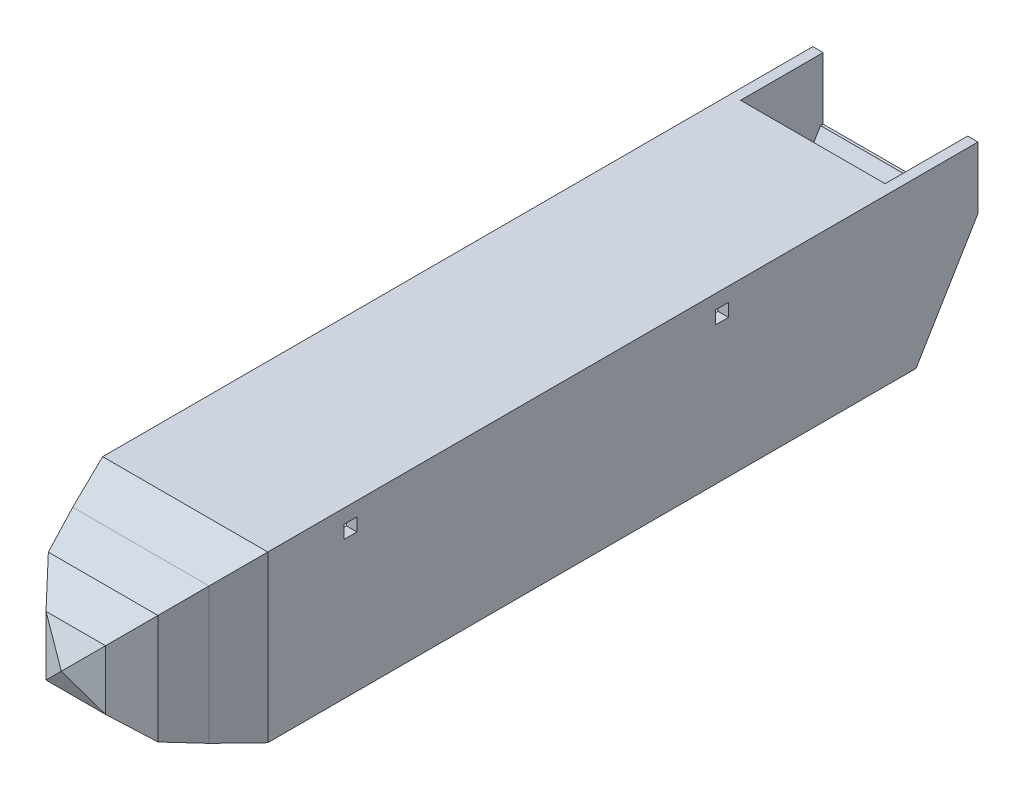
SolidWorks part; units mm, degrees
material "Balsa"
ref_plane "Front Plane" through (0, 0, 0) normal (0, 0, 1) x (1, 0, 0)
ref_plane "Top Plane" through (0, 0, 0) normal (0, 1, 0) x (1, 0, 0)
ref_plane "Right Plane" through (0, 0, 0) normal (1, 0, 0) x (0, 0, -1)
sketch "Sketch1" plane through (0, 0, 0) normal (0, 0, 1) x (1, 0, 0)
  line L1 (-50.8, -50.8) -> (50.8, -50.8)
  line L2 (-50.8, -50.8) -> (-50.8, 50.8)
  line L3 (-50.8, 50.8) -> (50.8, 50.8)
  line L4 (50.8, -50.8) -> (50.8, 50.8)
  line L5 (-50.8, -50.8) -> (50.8, 50.8) construction
  line L6 (-50.8, 50.8) -> (50.8, -50.8) construction
  point P0 (0, 0)
  dimension "D1" = 101.6
extrude "Boss-Extrude1" add sketch "Sketch1" along normal blind 436.88 contours L2 L1 L4 L3
ref_plane "Plane1" through (0, 0, 464.1566) normal (0, 0, 1) x (1, 0, 0)
sketch "Sketch3" plane through (0, 0, 464.1566) normal (0, 0, 1) x (1, 0, 0)
  line L1 (-41.9373, -41.9373) -> (41.9373, -41.9373)
  line L2 (-41.9373, -41.9373) -> (-41.9373, 41.9373)
  line L3 (-41.9373, 41.9373) -> (41.9373, 41.9373)
  line L4 (41.9373, -41.9373) -> (41.9373, 41.9373)
  line L5 (-41.9373, -41.9373) -> (41.9373, 41.9373) construction
  line L6 (-41.9373, 41.9373) -> (41.9373, -41.9373) construction
  point P0 (0, 0)
  dimension "D1" = 83.8746
  dimension "D2" = 83.8746
sketch "Sketch5" plane through (0, 0, 436.88) normal (0, 0, 1) x (1, 0, 0)
  line L0 (50.8, -50.8) -> (50.8, 50.8) construction
  line L1 (-50.8, 50.8) -> (50.8, 50.8) construction
  line L2 (-50.8, -50.8) -> (-50.8, 50.8) construction
  line L3 (-50.8, -50.8) -> (50.8, -50.8) construction
  line L4 (50.8, -50.8) -> (50.8, 50.8)
  line L5 (-50.8, 50.8) -> (50.8, 50.8)
  line L6 (-50.8, -50.8) -> (-50.8, 50.8)
  line L7 (-50.8, -50.8) -> (50.8, -50.8)
  dimension "D1" = 101.6
  dimension "D2" = 101.6
loft "Loft2" add profiles "Sketch5", "Sketch3" connector at (-50.8, 50.8, 436.88) connector at (-41.9373, 41.9373, 464.1566)
ref_plane "Plane2" through (0, 0, 487.3594) normal (0, 0, 1) x (1, 0, 0)
sketch "Sketch6" plane through (0, 0, 487.3594) normal (0, 0, 1) x (1, 0, 0)
  line L1 (-33.716, -33.716) -> (33.716, -33.716)
  line L2 (-33.716, -33.716) -> (-33.716, 33.716)
  line L3 (-33.716, 33.716) -> (33.716, 33.716)
  line L4 (33.716, -33.716) -> (33.716, 33.716)
  line L5 (-33.716, -33.716) -> (33.716, 33.716) construction
  line L6 (-33.716, 33.716) -> (33.716, -33.716) construction
  point P0 (0, 0)
loft "Loft3" add profiles "Sketch3<6>", "Sketch6" connector at (-41.9373, 41.9373, 464.1566) connector at (-33.716, 33.716, 487.3594)
sketch "Sketch3<6>" plane through (0, 0, 464.1566) normal (0, 0, 1) x (1, 0, 0) same geometry as "Sketch3"
ref_plane "Plane3" through (0, 0, 504.2173) normal (0, 0, 1) x (1, 0, 0)
sketch "Sketch7" plane through (0, 0, 504.2173) normal (0, 0, 1) x (1, 0, 0)
  line L5 (-41.9373, -41.9373) -> (41.9373, 41.9373) construction
  line L6 (-18.3041, -18.3041) -> (18.3041, -18.3041)
  line L8 (-18.3041, -18.3041) -> (-18.3041, 18.3041)
  line L9 (-18.3041, 18.3041) -> (18.3041, 18.3041)
  line L10 (18.3041, -18.3041) -> (18.3041, 18.3041)
  line L11 (-18.3041, -18.3041) -> (18.3041, 18.3041) construction
  line L12 (-18.3041, 18.3041) -> (18.3041, -18.3041) construction
  point P1 (0, 0)
loft "Loft4" add profiles "Sketch6<4>", "Sketch7" connector at (33.716, 33.716, 487.3594) connector at (18.3041, 18.3041, 504.2173)
sketch "Sketch6<4>" plane through (0, 0, 487.3594) normal (0, 0, 1) x (1, 0, 0) same geometry as "Sketch6"
sketch3d "3DSketch1" plane through (0, 0, 0) normal (0, 0, 1) x (1, 0, 0)
  dimension "D1" = 8.8627
sketch "Sketch8" plane through (0, 0, 513.08) normal (0, 0, 1) x (1, 0, 0)
  point P0 (0, 0)
loft "Loft5" add profiles "Sketch8", "Sketch7<5>"
sketch "Sketch7<5>" plane through (0, 0, 504.2173) normal (0, 0, 1) x (1, 0, 0) same geometry as "Sketch7"
shell "Shell1" thickness 6.35 removed face at (0, 0, 0)
sketch "Sketch9" plane through (50.8, 0, 0) normal (1, 0, 0) x (0, 0, -1)
  line L0 (-436.88, 50.8) -> (-436.88, 38.1)
  line L1 (-436.88, -50.8) -> (-436.88, 50.8) construction
  line L2 (-436.88, 38.1) -> (-386.08, 38.1)
  line L3 (-386.08, 38.1) -> (-157.48, 38.1)
  line L5 (-390.0805, 34.0995) -> (-382.0795, 34.0995)
  line L6 (-390.0805, 34.0995) -> (-390.0805, 42.1005)
  line L7 (-390.0805, 42.1005) -> (-382.0795, 42.1005)
  line L8 (-382.0795, 34.0995) -> (-382.0795, 42.1005)
  line L9 (-390.0805, 34.0995) -> (-382.0795, 42.1005) construction
  line L10 (-390.0805, 42.1005) -> (-382.0795, 34.0995) construction
  line L11 (-161.4805, 34.0995) -> (-153.4795, 34.0995)
  line L12 (-161.4805, 34.0995) -> (-161.4805, 42.1005)
  line L13 (-161.4805, 42.1005) -> (-153.4795, 42.1005)
  line L14 (-153.4795, 34.0995) -> (-153.4795, 42.1005)
  line L15 (-161.4805, 34.0995) -> (-153.4795, 42.1005) construction
  line L16 (-161.4805, 42.1005) -> (-153.4795, 34.0995) construction
  dimension "D4" = 8.001
  dimension "D5" = 8.001
  dimension "D1" = 12.7
  dimension "D2" = 50.8
  dimension "D3" = 228.6
  dimension "D6" = 8.001
  dimension "D7" = 8.001
extrude "Cut-Extrude1" cut sketch "Sketch9" against normal through all contours L5 L8 L3 L2 L6 | L3 L8 L7 L6 L2 | L11 L14 L13 L12 region at (50.8, 40.1002, 386.08) region at (50.8, 36.0997, 386.08) region at (50.8, 40.1002, 161.3673)
sketch "Sketch10" plane through (50.8, 0, 0) normal (1, 0, 0) x (0, 0, -1)
  line L0 (-436.88, 50.8) -> (0, 50.8) construction
  line L3 (0, 50.8) -> (-68.9584, 50.8)
  line L4 (-68.9584, -50.8) -> (-68.9584, 50.8)
  line L5 (0, 50.8) -> (0, 12.7)
  line L6 (0, -50.8) -> (-38.1, -50.8)
  line L7 (0, 12.7) -> (-38.1, -50.8)
  line L8 (0, 12.7) -> (0, -50.8)
  line M16 (0, -50.8) -> (0, 50.8)
  line M19 (-436.88, -50.8) -> (0, -50.8)
  dimension "D1" = 38.1
  dimension "D2" = 38.1
  dimension "D3" = 63.5
extrude "Cut-Extrude2" cut sketch "Sketch10" against normal through all contours L7 M16 M19 region at (50.8, -29.6333, 12.7)
sketch "Sketch11" plane through (50.8, 0, 0) normal (1, 0, 0) x (0, 0, -1)
  line L0 (-38.1, -50.8) -> (-39.6875, -50.8)
  line L1 (-436.88, -50.8) -> (-38.1, -50.8) construction
  line L2 (0, 50.8) -> (-1.5875, 50.8)
  line L3 (-436.88, 50.8) -> (0, 50.8) construction
  line L4 (-1.5875, 50.8) -> (-1.5875, 12.7)
  line L5 (0, 50.8) -> (0, 12.7)
  line L6 (-1.5875, 12.7) -> (-39.6875, -50.8)
  line L7 (0, 12.7) -> (-38.1, -50.8)
  dimension "D1" = 1.5875
  dimension "D2" = 1.5875
extrude "Boss-Extrude2" add sketch "Sketch11" against normal blind 101.6
sketch "Sketch12" plane through (0, 0, 0) normal (0, 0, -1) x (-1, 0, 0)
  line L0 (-50.8, 50.8) -> (-44.45, 50.8)
  line L1 (50.8, 50.8) -> (-50.8, 50.8) construction
  line L2 (50.8, 12.7) -> (-50.8, 12.7) construction
  line L3 (-44.45, 50.8) -> (44.45, 50.8)
  line L4 (-44.45, 50.8) -> (-44.45, 12.7)
  line L5 (-44.45, 12.7) -> (44.45, 12.7)
  line L6 (44.45, 50.8) -> (44.45, 12.7)
  line M7 (-50.8, 12.7) -> (50.8, 12.7)
  line M9 (50.8, 50.8) -> (-50.8, 50.8)
  dimension "D1" = 6.35
  dimension "D2" = 88.9
extrude "Cut-Extrude3" cut sketch "Sketch12" against normal blind 50.8 contours L6 L4 M9 M7 region at (0, 31.75, 0)
equation "\"Fuse_Diam\"= 4"
equation "\"D2@Sketch1\"=\"Fuse_Diam\""
equation "\"D1@Sketch1\"=\"Fuse_Diam\""
equation "\"Magic Line\"= 3 / ( cos ( 18 ) + cos ( 2 * 18 ) + cos ( 3 * 18 ) + cos ( 4 * 18 ) )"
equation "\"Second Stage Cone\"= 3.30215"
equation "\"D1@Sketch3\"=\"Second Stage Cone\""
equation "\"D2@Sketch3\"=\"Second Stage Cone\""
equation "\"Thick\"=0.25"
equation "\"D1@Sketch12\"=\"Thick\""
equation "\"D1@Shell1\"=\"Thick\""
equation "\"attachment\"=3.5"
equation "\"D2@Sketch12\"=\"attachment\""
